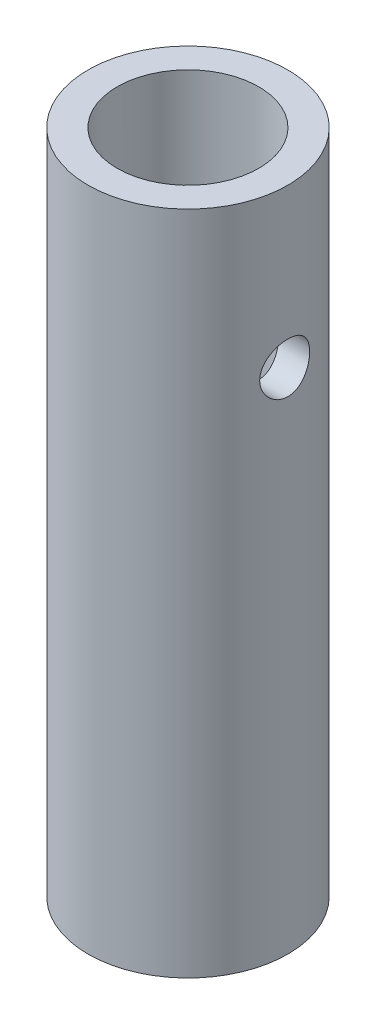
SolidWorks part; units mm, degrees
ref_plane "Front Plane" through (0, 0, 0) normal (0, 0, 1) x (1, 0, 0)
ref_plane "Top Plane" through (0, 0, 0) normal (0, 1, 0) x (1, 0, 0)
ref_plane "Right Plane" through (0, 0, 0) normal (1, 0, 0) x (0, 0, -1)
sketch "Sketch1" plane through (0, 0, 0) normal (0, 1, 0) x (1, 0, 0)
  circle A0 centre (0, 0) radius 4.25
  circle A1 centre (0, 0) radius 6
  dimension "D1" = 8.5
  dimension "D2" = 12
extrude "Boss-Extrude1" add sketch "Sketch1" along normal blind 40
sketch "Sketch2" plane through (0, 0, 0) normal (1, 0, 0) x (0, 0, -1)
  line L0 (0, 0) -> (0, 32) construction
  line L1 (0, 32) -> (0, 30.5)
  circle A0 centre (0, 30.5) radius 1.5
  dimension "D1" = 32
  dimension "D2" = 1.5
extrude "Cut-Extrude1" cut sketch "Sketch2" against normal blind 40 and the other way blind 40 contours A0
